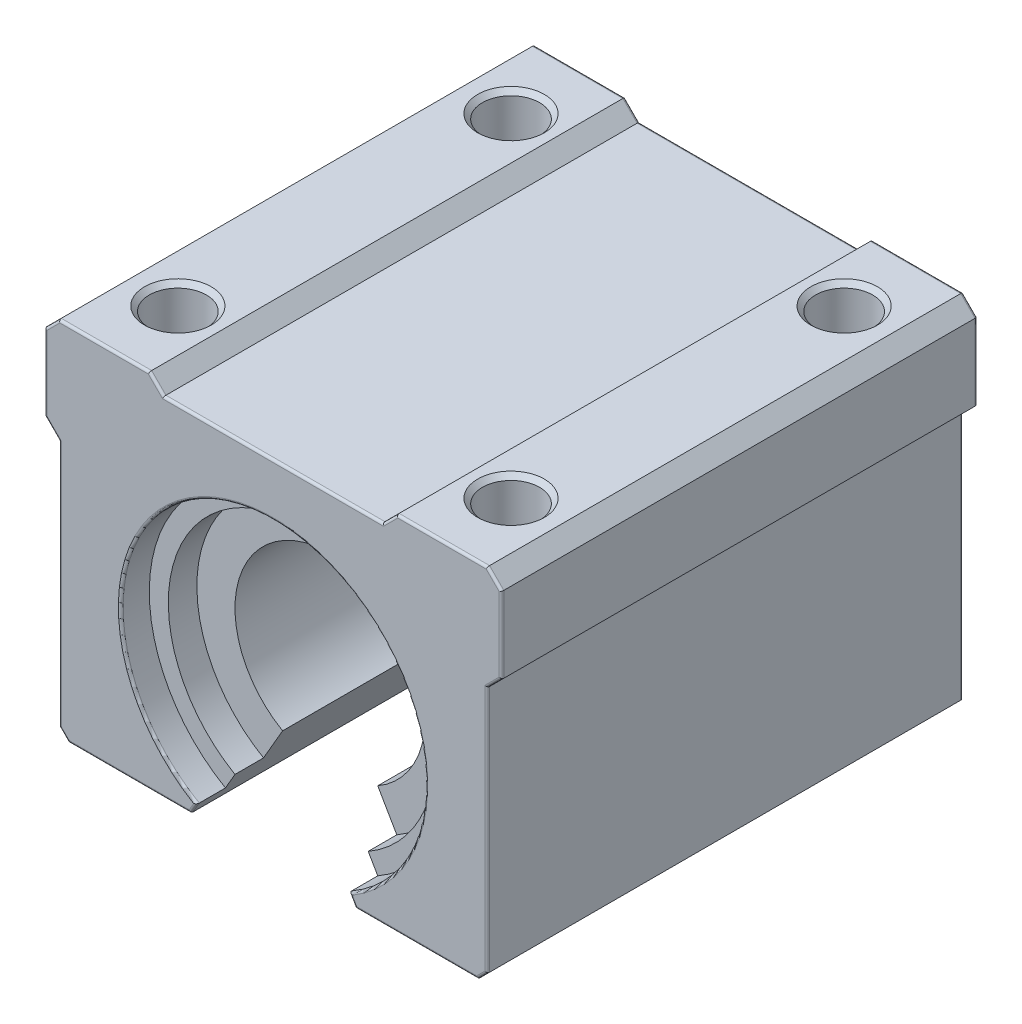
SolidWorks part; units mm, degrees
ref_plane "Front Plane" through (0, 0, 0) normal (0, 0, 1) x (1, 0, 0)
ref_plane "Top Plane" through (0, 0, 0) normal (0, 1, 0) x (1, 0, 0)
ref_plane "Right Plane" through (0, 0, 0) normal (1, 0, 0) x (0, 0, -1)
sketch "Sketch1" plane through (0, 0, 0) normal (0, 0, 1) x (1, 0, 0)
  line L0 (0, 29.1887) -> (0, -22.3517) construction
  line L1 (-34.9739, 0) -> (34.4479, 0) construction
  line L2 (-22.5, 12) -> (-22.5, -15)
  line L3 (24, 12) -> (22.5, 12)
  line L4 (24, 12) -> (24, 23)
  line L5 (24, 23) -> (11.5, 23)
  line L6 (-24, 12) -> (-24, 23)
  line L7 (24, 12) -> (-24, 23) construction
  line L8 (24, 23) -> (-24, 12) construction
  line L9 (-22.5, -15) -> (22.5, -15)
  line L10 (22.5, 12) -> (22.5, -15)
  line L11 (-22.5, 12) -> (-24, 12)
  line L12 (11.5, 21.5) -> (-11.5, 21.5)
  line L13 (-11.5, 21.5) -> (-11.5, 23)
  line L14 (11.5, 21.5) -> (11.5, 23)
  line L15 (-11.5, 23) -> (-24, 23)
  circle A0 centre (0, 0) radius 10 construction
  point P7 (0, 17.5)
  point P18 (0, -15)
  point P22 (0, 21.5)
  dimension "D1" = 20
  dimension "D4" = 23
  dimension "D2" = 48
  dimension "D3" = 11
  dimension "D5" = 38
  dimension "D6" = 22.5
  dimension "D7" = 23
  dimension "D8" = 1.5
  dimension "D9" = 1.5
extrude "Boss-Extrude2" add sketch "Sketch1" along normal mid plane 50
chamfer "Chamfer3" distance 1.5 angle 45 6 edges at (24, 23, 0) (24, 12, 0) (11.5, 23, 0) (-11.5, 23, 0) (-24, 12, 0) (-24, 23, 0)
chamfer "Chamfer4" distance 1 angle 45 2 edges at (22.5, -15, 0) (-22.5, -15, 0)
sketch "Sketch3" plane through (0, 21.5, 0) normal (0, 1, 0) x (1, 0, 0)
  line L0 (0, 31.926) -> (0, -36.2484) construction
  line L1 (42.0099, 0) -> (-40.1024, 0) construction
  circle A0 centre (-17.5, 17.5) radius 3
  circle A1 centre (17.5, 17.5) radius 3
  circle A2 centre (17.5, -17.5) radius 3
  circle A3 centre (-17.5, -17.5) radius 3
  dimension "D1" = 6
  dimension "D2" = 35
  dimension "D3" = 35
extrude "Cut-Extrude6" cut sketch "Sketch3" against normal blind 10.5 and the other way up to next
sketch "Sketch4" plane through (0, 0, 25) normal (0, 0, 1) x (1, 0, 0)
  circle A0 centre (0, 0) radius 10
  point P2 (0, 0)
  dimension "D1" = 20
extrude "Cut-Extrude8" cut sketch "Sketch4" against normal through all both
sketch "Sketch6" plane through (0, 0, 25) normal (0, 0, 1) x (1, 0, 0)
  line L0 (0, 22.6334) -> (0, -18.7712) construction
  line L1 (9.0802, -15.7273) -> (-9.0802, -15.7273)
  line L2 (-9.0802, -15.7273) -> (-5, -8.6603)
  line L3 (-5, -8.6603) -> (5, -8.6603)
  line L4 (9.0802, -15.7273) -> (5, -8.6603)
  line L5 (24, 13.5) -> (24, 21.5) construction
  circle A1 centre (0, 0) radius 10 construction
  point P10 (0, -15.7273)
  point P11 (0, -8.6603)
  dimension "D1" = 10
  dimension "D2" = 60
  dimension "D3" = 14.9198
extrude "Cut-Extrude9" cut sketch "Sketch6" against normal through all both
sketch "Sketch7" plane through (0, 0, 25) normal (0, 0, 1) x (1, 0, 0)
  circle A0 centre (0, 0) radius 16
  dimension "D1" = 32
extrude "Cut-Extrude10" cut sketch "Sketch7" against normal blind 3
sketch "Sketch8" plane through (0, 0, -25) normal (0, 0, -1) x (-1, 0, 0)
  circle A0 centre (0, 0) radius 16
  dimension "D1" = 32
extrude "Cut-Extrude11" cut sketch "Sketch8" against normal blind 3
sketch "Sketch9" plane through (0, 0, 22) normal (0, 0, 1) x (1, 0, 0)
  circle A0 centre (0, 0) radius 14
  dimension "D1" = 28
extrude "Cut-Extrude12" cut sketch "Sketch9" against normal blind 3
sketch "Sketch10" plane through (0, 0, -22) normal (0, 0, -1) x (-1, 0, 0)
  circle A0 centre (0, 0) radius 14
  dimension "D1" = 28
extrude "Cut-Extrude13" cut sketch "Sketch10" against normal blind 3
chamfer "Chamfer5" distance 0.5 angle 45 4 edges at (17.5, 23, 14.5) (17.5, 23, -20.5) (-14.5, 23, -17.5) (-14.5, 23, 17.5)
fillet "Fillet1" radius 0.25 20 edges at (15.0801, -15, -25) (22, -14.5, -25) (22.5, -1, -25) (23.25, 12.75, -25) (24, 17.5, -25) (23.25, 22.25, -25) (17.75, 23, -25) (12.25, 22.25, -25) (0, 21.5, -25) (-12.25, 22.25, -25) (-17.75, 23, -25) (-23.25, 22.25, -25) (-24, 17.5, -25) (-23.25, 12.75, -25) (-22.5, -1, -25) (-22, -14.5, -25) (-15.0801, -15, -25) (-8.3301, -14.4282, -25) (0, 16, -25) (8.3301, -14.4282, -25)
fillet "Fillet3" radius 0.25 20 edges at (-8.3301, -14.4282, 25) (-15.0801, -15, 25) (-22, -14.5, 25) (-22.5, -1, 25) (-23.25, 12.75, 25) (-24, 17.5, 25) (-23.25, 22.25, 25) (-17.75, 23, 25) (-12.25, 22.25, 25) (0, 21.5, 25) (12.25, 22.25, 25) (17.75, 23, 25) (23.25, 22.25, 25) (24, 17.5, 25) (23.25, 12.75, 25) (22.5, -1, 25) (22, -14.5, 25) (15.0801, -15, 25) (8.3301, -14.4282, 25) (0, 16, 25)
